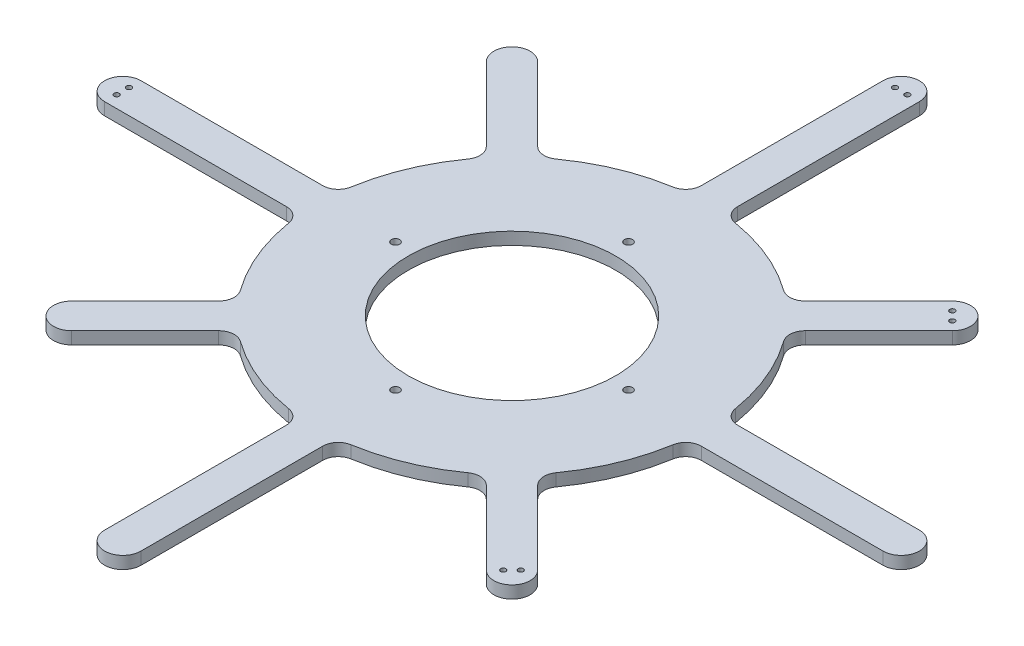
SolidWorks part; units mm, degrees
ref_plane "Front" through (0, 0, 0) normal (0, 0, 1) x (1, 0, 0)
ref_plane "Top" through (0, 0, 0) normal (0, 1, 0) x (1, 0, 0)
ref_plane "Right" through (0, 0, 0) normal (1, 0, 0) x (0, 0, -1)
sketch "Sketch1" plane through (0, 0, 0) normal (0, 1, 0) x (1, 0, 0)
  circle A0 centre (0, 0) radius 37.5
  circle A1 centre (0, 0) radius 20
  dimension "D1" = 75
  dimension "D2" = 40
base flange "Base-Flange1" sketch "Sketch1" thickness 2.3812 reverse thickness direction no parameters "D1"=10
sketch "Sketch6" plane through (0, 0, 0) normal (0, 1, 0) x (1, 0, 0)
  line L0 (-3.5, 75) -> (-3.5, 37.3363)
  line L1 (-3.5, 37.3363) -> (3.5, 37.3363)
  line L2 (3.5, 37.3363) -> (3.5, 75)
  line L3 (0, 37.3363) -> (0, 0) construction
  arc A0 (3.5, 75) -> (-3.5, 75) centre (0, 75) ccw
  circle A1 centre (0, 0) radius 37.5 construction
  dimension "D1" = 75
  dimension "D2" = 7
extrude "Boss-Extrude1" add sketch "Sketch6" against normal blind 2.3813
sketch "Sketch9" plane through (0, 0, 0) normal (0, 1, 0) x (1, 0, 0)
  line L0 (23.9259, 28.8756) -> (28.8756, 23.9259)
  line L1 (28.8756, 23.9259) -> (44.9013, 39.9515)
  line L2 (39.9515, 44.9013) -> (23.9259, 28.8756)
  line L3 (0, 0) -> (42.4264, 42.4264) construction
  line L4 (3.5, 37.3363) -> (3.5, 75) construction
  arc A0 (44.9013, 39.9515) -> (39.9515, 44.9013) centre (42.4264, 42.4264) ccw
  arc A1 (-3.5, 37.3363) -> (3.5, 37.3363) centre (0, 0) ccw construction
  arc A2 (3.5, 75) -> (-3.5, 75) centre (0, 75) ccw construction
  dimension "D1" = 45
  dimension "D2" = 60
extrude "Boss-Extrude2" add sketch "Sketch9" against normal blind 2.3812
fillet "Fillet1" radius 3 4 edges at (-3.5, -1.1906, -37.3363) (3.5, -1.1906, -37.3363) (28.8756, -1.1906, -23.9259) (23.9259, -1.1906, -28.8756)
pattern_circular "CirPattern1" count 4 every 90 about axis through (0, 0, 0) along (0, 1, 0) of "Boss-Extrude1", "Fillet1", "Boss-Extrude2"
sketch "Sketch7" plane through (0, 0, 0) normal (0, 1, 0) x (1, 0, 0)
  line L0 (-1.1906, 75) -> (1.1906, 75) construction
  line L1 (0, 0) -> (42.4264, 42.4264) construction
  line L2 (0, 0) -> (-75, 0) construction
  line L3 (0, 0) -> (42.4264, -42.4264) construction
  line L4 (41.5845, -43.2683) -> (43.2683, -41.5845) construction
  line L5 (-75, 1.1906) -> (-75, -1.1906) construction
  line L6 (43.2683, 41.5845) -> (41.5845, 43.2683) construction
  line L9 (30.7415, 25.7917) -> (44.9013, 39.9515) construction
  line L10 (-39.975, 3.5) -> (-75, 3.5) construction
  line L12 (44.9013, -39.9515) -> (30.7415, -25.7917) construction
  circle A0 centre (-1.1906, 75) radius 0.5
  circle A1 centre (1.1906, 75) radius 0.5
  circle A2 centre (41.5845, 43.2683) radius 0.5
  circle A3 centre (43.2683, 41.5845) radius 0.5
  circle A4 centre (-75, -1.1906) radius 0.5
  circle A5 centre (-75, 1.1906) radius 0.5
  circle A6 centre (43.2683, -41.5845) radius 0.5
  circle A7 centre (41.5845, -43.2683) radius 0.5
  dimension "D2" = 1
  dimension "D1" = 2.3812
extrude "Cut-Extrude1" cut sketch "Sketch7" against normal through all normal cut yes
sketch "Sketch10" plane through (0, 0, 0) normal (0, 1, 0) x (1, 0, 0)
  line L0 (1.1225, -23.5732) -> (-23.5732, 1.1225) construction
  line L1 (-23.5732, 1.1225) -> (-1.1225, 23.5732) construction
  line L2 (-1.1225, 23.5732) -> (23.5732, -1.1225) construction
  line L3 (23.5732, -1.1225) -> (1.1225, -23.5732) construction
  line L4 (-12.3479, 12.3479) -> (0, 0) construction
  line L5 (-3.5, 75) -> (-3.5, 39.975) construction
  line L6 (-23.5732, 1.1225) -> (23.5732, -1.1225) construction
  circle A0 centre (-23.5732, 1.1225) radius 0.7937
  circle A1 centre (-1.1225, 23.5732) radius 0.7937
  circle A2 centre (23.5732, -1.1225) radius 0.7937
  circle A3 centre (1.1225, -23.5732) radius 0.7937
  dimension "D4" = 1.5875
  dimension "D1" = 31.75
  dimension "D2" = 34.925
  dimension "D3" = 45
extrude "Cut-Extrude2" cut sketch "Sketch10" against normal through all normal cut yes
sketch "Sketch11" plane through (0, 0, 0) normal (0, 1, 0) x (1, 0, 0)
  line L0 (-30.8696, 19.6443) -> (-19.6443, 30.8696)
  line L1 (19.6443, -30.8696) -> (30.8696, -19.6443)
sketch "Bend-Lines1" [suppressed] plane through (0, 0, 0) normal (0, 1, 0) x (1, 0, 0)
sketch "Bounding-Box1" [suppressed] plane through (0, 0, 0) normal (0, 1, 0) x (1, 0, 0)
sheet metal parameters "Sheet-Metal1" thickness 2.3812 parameters "D1"=10
flat pattern "Flat-Pattern1" [suppressed]
sketch "Bend-Lines2" plane through (0, 0, 0) normal (0, 1, 0) x (1, 0, 0)
sketch "Bounding-Box2" [suppressed] plane through (0, 0, 0) normal (0, 1, 0) x (1, 0, 0)
sheet metal parameters "Sheet-Metal2" thickness 2.3812 parameters "D1"=10
flat pattern "Flat-Pattern1"
sketch "Bend-Lines2" plane through (0, 0, 0) normal (0, 1, 0) x (1, 0, 0)
sketch "Bounding-Box2" [suppressed] plane through (0, 0, 0) normal (0, 1, 0) x (1, 0, 0)
sheet metal parameters "Sheet-Metal3" thickness 2.3812 parameters "D1"=10
flat pattern "Flat-Pattern1"
sketch "Bend-Lines2" plane through (0, 0, 0) normal (0, 1, 0) x (1, 0, 0)
sketch "Bounding-Box2" [suppressed] plane through (0, 0, 0) normal (0, 1, 0) x (1, 0, 0)
sheet metal parameters "Sheet-Metal4" thickness 2.3812 parameters "D1"=10
flat pattern "Flat-Pattern1"
sketch "Bend-Lines2" plane through (0, 0, 0) normal (0, 1, 0) x (1, 0, 0)
sketch "Bounding-Box2" [suppressed] plane through (0, 0, 0) normal (0, 1, 0) x (1, 0, 0)
sheet metal parameters "Sheet-Metal5" thickness 2.3812 parameters "D1"=10
flat pattern "Flat-Pattern1"
sketch "Bend-Lines2" plane through (0, 0, 0) normal (0, 1, 0) x (1, 0, 0)
sketch "Bounding-Box2" [suppressed] plane through (0, 0, 0) normal (0, 1, 0) x (1, 0, 0)
sheet metal parameters "Sheet-Metal6" thickness 2.3812 parameters "D1"=10
flat pattern "Flat-Pattern1"
sketch "Bend-Lines2" plane through (0, 0, 0) normal (0, 1, 0) x (1, 0, 0)
sketch3d "Bounding-Box2" [suppressed]
  line L0 (-88.3205, -11.6023, 0) -> (11.6023, -88.3205, 0) construction
  line L1 (-11.6023, 88.3205, 0) -> (88.3205, 11.6023, 0) construction
  line L2 (-88.3205, -11.6023, 0) -> (-11.6023, 88.3205, 0) construction
  line L3 (11.6023, -88.3205, 0) -> (88.3205, 11.6023, 0) construction
